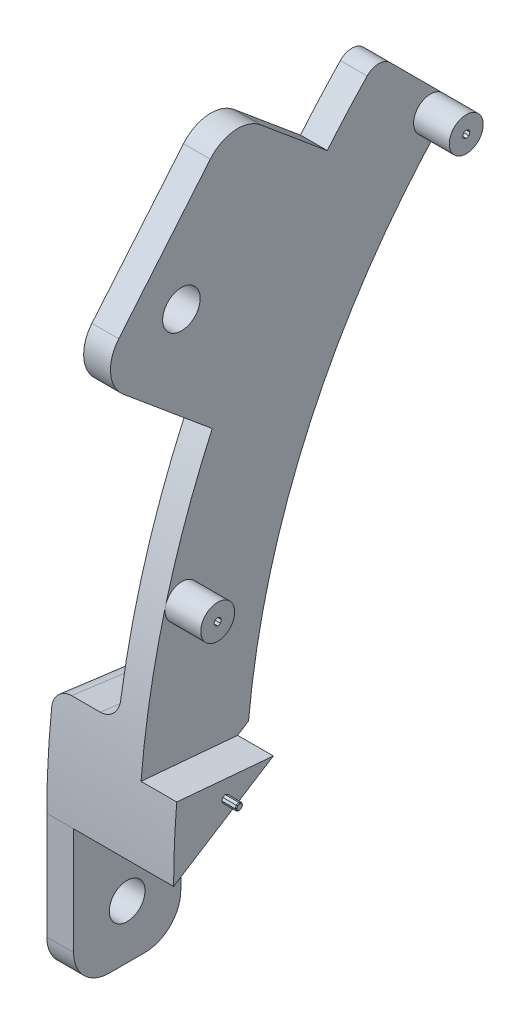
SolidWorks part; units mm, degrees
ref_plane "Front Plane" through (0, 0, 0) normal (0, 0, 1) x (1, 0, 0)
ref_plane "Top Plane" through (0, 0, 0) normal (0, 1, 0) x (1, 0, 0)
ref_plane "Right Plane" through (0, 0, 0) normal (1, 0, 0) x (0, 0, -1)
sketch "Sketch2" plane through (0, 0, 0) normal (1, 0, 0) x (0, 0, -1)
  line L0 (-197.177, 0) -> (-167.177, 0)
  line L1 (-129.8116, 162.6346) -> (-108.5984, 141.4214)
  arc A0 (-167.177, 0) -> (-108.5984, 141.4214) centre (32.823, 0) cw
  arc A1 (-197.177, 0) -> (-129.8116, 162.6346) centre (32.823, 0) cw
  dimension "D4" = 200
  dimension "D1" = 30
  dimension "D2" = 30
  dimension "D3" = 45
extrude "Curve Main Body" add sketch "Sketch2" along normal blind 35.5
sketch "Sketch6" plane through (35.5, 0, 0) normal (1, 0, 0) x (0, 0, -1)
  line L0 (-165.466, 26.1052) -> (-195.2093, 30.021)
  line L1 (-108.5984, 141.4214) -> (-129.8116, 162.6346)
  line L2 (-197.177, 0) -> (-167.177, 0) construction
  arc A0 (-108.5984, 141.4214) -> (-167.177, 0) centre (32.823, 0) ccw construction
  arc A1 (-129.8116, 162.6346) -> (-197.177, 0) centre (32.823, 0) ccw construction
  arc A2 (-165.466, 26.1052) -> (-108.5984, 141.4214) centre (32.823, 0) cw
  arc A3 (-129.8116, 162.6346) -> (-195.2093, 30.021) centre (32.823, 0) ccw
  dimension "D1" = 30
  dimension "D2" = 7.5
extrude "Cut-Extrude2" cut sketch "Sketch6" against normal offset from surface (18 mm away) 17.5 up to face at (0, 79.1455, 158.2511)
sketch "Sketch7" plane through (0, 0, 0) normal (-1, 0, 0) x (0, 0, 1)
  line L0 (166.416, 17.4311) -> (196.3018, 20.0458)
  line L1 (167.177, 0) -> (197.177, 0) construction
  line L3 (129.8116, 162.6346) -> (108.5984, 141.4214)
  arc A0 (167.177, 0) -> (108.5984, 141.4214) centre (-32.823, 0) ccw construction
  arc A1 (197.177, 0) -> (129.8116, 162.6346) centre (-32.823, 0) ccw construction
  arc A2 (196.3018, 20.0458) -> (129.8116, 162.6346) centre (-32.823, 0) ccw
  arc A3 (108.5984, 141.4214) -> (166.416, 17.4311) centre (-32.823, 0) cw
  dimension "D1" = 30
  dimension "D2" = 5
extrude "Cut-Extrude3" cut sketch "Sketch7" against normal offset from surface (10 mm away) 7.5 up to face at (17.5, 92.5688, 154.888)
fillet "Fillet3" radius 5 2 edges at (35.5, 28.0631, 180.3377) (17.5, 28.0631, 180.3377)
mirror "Mirror3" about plane through (0, 0, -32.823) normal (-1, 0, 0) of "Curve Main Body", "Cut-Extrude2", "Cut-Extrude3", "Fillet3"
sketch "Sketch14" plane through (0, 0, 0) normal (0, -1, 0) x (1, 0, 0)
  line L0 (35.5, 167.177) -> (-35.5, 167.177) construction
  line L1 (-35.5, 197.177) -> (-28, 197.177)
  line L2 (-35.5, 197.177) -> (-35.5, 167.177)
  line L3 (-35.5, 167.177) -> (-28, 167.177)
  line L4 (-28, 197.177) -> (-28, 167.177)
  line L5 (0, 197.177) -> (0, 167.177) construction
  line L6 (35.5, 197.177) -> (-35.5, 197.177) construction
  line L7 (28, 197.177) -> (28, 167.177)
  line L8 (35.5, 167.177) -> (28, 167.177)
  line L9 (35.5, 197.177) -> (35.5, 167.177)
  line L10 (35.5, 197.177) -> (28, 197.177)
  dimension "D1" = 7.5
extrude "Boss-Extrude9" add sketch "Sketch14" along normal blind 40
sketch "Sketch17" plane through (-10, 0, 0) normal (1, 0, 0) x (0, 0, -1)
  line L0 (-108.5984, 141.4214) -> (-129.8116, 162.6346) construction
  line L2 (-115.2769, 141.3824) -> (-191.7402, 49.7129) construction
  line L3 (-196.3018, 20.0458) -> (-154.4398, 70.2329) construction
  arc A0 (-108.5984, 141.4214) -> (-166.416, 17.4311) centre (32.823, 0) ccw construction
  circle A1 centre (-115.2769, 141.3824) radius 4.75
  circle A4 centre (-184.8336, 57.9931) radius 4.75
  arc A5 (-129.8116, 162.6346) -> (-196.3018, 20.0458) centre (32.823, 0) ccw construction
  dimension "D3" = 9.5
  dimension "D2" = 15.5
extrude "Boss-Extrude6" add sketch "Sketch17" along normal blind 25
sketch "Sketch18" plane through (-10, 0, 0) normal (1, 0, 0) x (0, 0, -1)
  line L0 (-184.8336, 57.9931) -> (-115.2769, 141.3824) construction
  line L1 (-150.0552, 99.6877) -> (-196.1307, 138.1202) construction
  line L2 (-208.9415, 122.7617) -> (-162.8661, 84.3292)
  line L3 (-208.9415, 122.7617) -> (-170.5091, 168.8371)
  line L4 (-162.8661, 84.3292) -> (-124.4336, 130.4047)
  line L5 (-170.5091, 168.8371) -> (-124.4336, 130.4047)
  circle A1 centre (-184.8336, 57.9931) radius 4.75 construction
  point P5 (0, 0)
  point P6 (0, 0)
  dimension "D1" = 60
  dimension "D2" = 20
  dimension "D3" = 60
extrude "Boss-Extrude7" add sketch "Sketch18" against normal up to surface (7.5 mm away) up to face at (-17.5, 94.9241, 154.1509)
sketch "Sketch21" plane through (0, 0, 0) normal (1, 0, 0) x (0, 0, -1)
  line L1 (-209.5581, 171.1954) -> (-104.3811, 171.1954)
  line L2 (-209.5581, 171.1954) -> (-209.5581, -48.5736)
  line L3 (-209.5581, -48.5736) -> (-104.3811, -48.5736)
  line L4 (-104.3811, 171.1954) -> (-104.3811, -48.5736)
extrude "Cut-Extrude5" cut sketch "Sketch21" along normal through all
chamfer "Chamfer2" distance 30 distance2 19 1 edges at (-14, 0, 167.177) first distance on face at (-14, 0, 182.177)
sketch "Sketch22" plane through (-28, 0, 0) normal (1, 0, 0) x (0, 0, -1)
  line L0 (-197.177, 0) -> (-167.177, 0) construction
  line L1 (-182.177, 0) -> (-182.177, -40) construction
  line L2 (-167.177, -40) -> (-197.177, -40) construction
  circle A0 centre (-182.177, -25) radius 5
  dimension "D2" = 10
  dimension "D1" = 25
extrude "Biceps Connection Hole" cut sketch "Sketch22" against normal through all
sketch "Sketch19" plane through (-10, 0, 0) normal (1, 0, 0) x (0, 0, -1)
  line L0 (-196.1307, 138.1202) -> (-143.5644, 94.2736) construction
  line L2 (-184.8336, 57.9931) -> (-115.2769, 141.3824) construction
  line L3 (-170.5091, 168.8371) -> (-208.9415, 122.7617) construction
  circle A2 centre (-184.8336, 57.9931) radius 4.75 construction
  circle A3 centre (-184.9958, 128.8323) radius 5.25
  arc A4 (-111.8412, 138.1025) -> (-166.2133, 19.6104) centre (32.823, 0) ccw construction
  point P2 (0, 0)
  point P13 (-150.0552, 99.6877)
  dimension "D1" = 45.5
  dimension "D2" = 10.5
extrude "Servo Hole" cut sketch "Sketch19" against normal through all both and the other way through all
sketch "Sketch23" plane through (0, 0, 0) normal (1, 0, 0) x (0, 0, -1)
  line L0 (-115.2769, 146.1324) -> (-115.2769, 136.6324) construction
  line L1 (-115.2769, 140.3574) -> (-114.5521, 140.6576)
  line L2 (-114.2519, 141.3824) -> (-114.5521, 142.1072)
  line L3 (-114.5521, 142.1072) -> (-115.2769, 142.4074)
  line L4 (-115.2769, 142.4074) -> (-116.0017, 142.1072)
  line L5 (-116.0017, 142.1072) -> (-116.3019, 141.3824)
  line L6 (-116.3019, 141.3824) -> (-116.0017, 140.6576)
  line L7 (-116.0017, 140.6576) -> (-115.2769, 140.3574)
  line L8 (-114.5521, 140.6576) -> (-114.2519, 141.3824)
  line L9 (-184.8336, 62.7431) -> (-184.8336, 53.2431) construction
  line L11 (-184.8336, 59.0181) -> (-185.5583, 58.7179)
  line L12 (-185.5583, 58.7179) -> (-185.8586, 57.9931)
  line L13 (-185.8586, 57.9931) -> (-185.5583, 57.2683)
  line L14 (-185.5583, 57.2683) -> (-184.8336, 56.9681)
  line L15 (-184.8336, 56.9681) -> (-184.1088, 57.2683)
  line L16 (-184.1088, 57.2683) -> (-183.8086, 57.9931)
  line L17 (-183.8086, 57.9931) -> (-184.1088, 58.7179)
  line L18 (-184.1088, 58.7179) -> (-184.8336, 59.0181)
  arc A0 (-111.9182, 144.7411) -> (-111.8412, 138.1025) centre (-115.2769, 141.3824) ccw construction
  circle A1 centre (-115.2769, 141.3824) radius 4.75 construction
  circle A2 centre (-115.2769, 141.3824) radius 1.025 construction
  circle A3 centre (-184.8336, 57.9931) radius 4.75 construction
  circle A4 centre (-184.8336, 57.9931) radius 4.75 construction
  circle A5 centre (-184.8336, 57.9931) radius 1.025 construction
  dimension "D1" = 2.05
  dimension "D2" = 2.05
extrude "Female Jack" cut sketch "Sketch23" against normal blind 5
sketch "Sketch25" plane through (0, 0, 0) normal (1, 0, 0) x (0, 0, -1)
  line L0 (-182.6483, 9.2015) -> (-182.177, -25) construction
  line L1 (-196.3018, 20.0458) -> (-169.2611, 17.6801) construction
  line L2 (-166.2133, 19.6104) -> (-197.177, 0) construction
  line L3 (-182.7815, 18.8629) -> (-182.6483, 9.2015) construction
  line L5 (-182.7287, 15.0321) -> (-183.4317, 14.7295)
  line L6 (-183.4317, 14.7295) -> (-183.7148, 14.0184)
  line L7 (-183.7148, 14.0184) -> (-183.4122, 13.3154)
  line L8 (-183.4122, 13.3154) -> (-182.7011, 13.0323)
  line L9 (-182.7011, 13.0323) -> (-181.9981, 13.3349)
  line L10 (-181.9981, 13.3349) -> (-181.715, 14.046)
  line L11 (-181.715, 14.046) -> (-182.0176, 14.749)
  line L12 (-182.0176, 14.749) -> (-182.7287, 15.0321)
  circle A1 centre (-182.7149, 14.0322) radius 1 construction
  point P1 (0, 0)
  point P5 (-182.6483, 9.2015)
  dimension "D1" = 2
extrude "Male Jack" add sketch "Sketch25" along normal blind 4
chamfer "Chamfer3" distance 0.2 8 edges at (4, 13.1739, 183.0567) (4, 13.1836, 182.3496) (4, 13.6905, 181.8566) (4, 14.3975, 181.8663) (4, 14.8906, 182.3731) (4, 14.8808, 183.0802) (4, 14.374, 183.5732) (4, 13.6669, 183.5635)
fillet "Biceps Connection Fillet" radius 10 2 edges at (-31.75, -40, 197.177) (-31.75, -40, 167.177)
fillet "Bow Connection Fillet" radius 4.5 2 edges at (-13.75, 162.6346, 129.8116) (-13.75, 141.4214, 108.5984)
fillet "Servo Hole Fillet" radius 10 2 edges at (-13.75, 168.8371, 170.5091) (-13.75, 122.7617, 208.9415)
